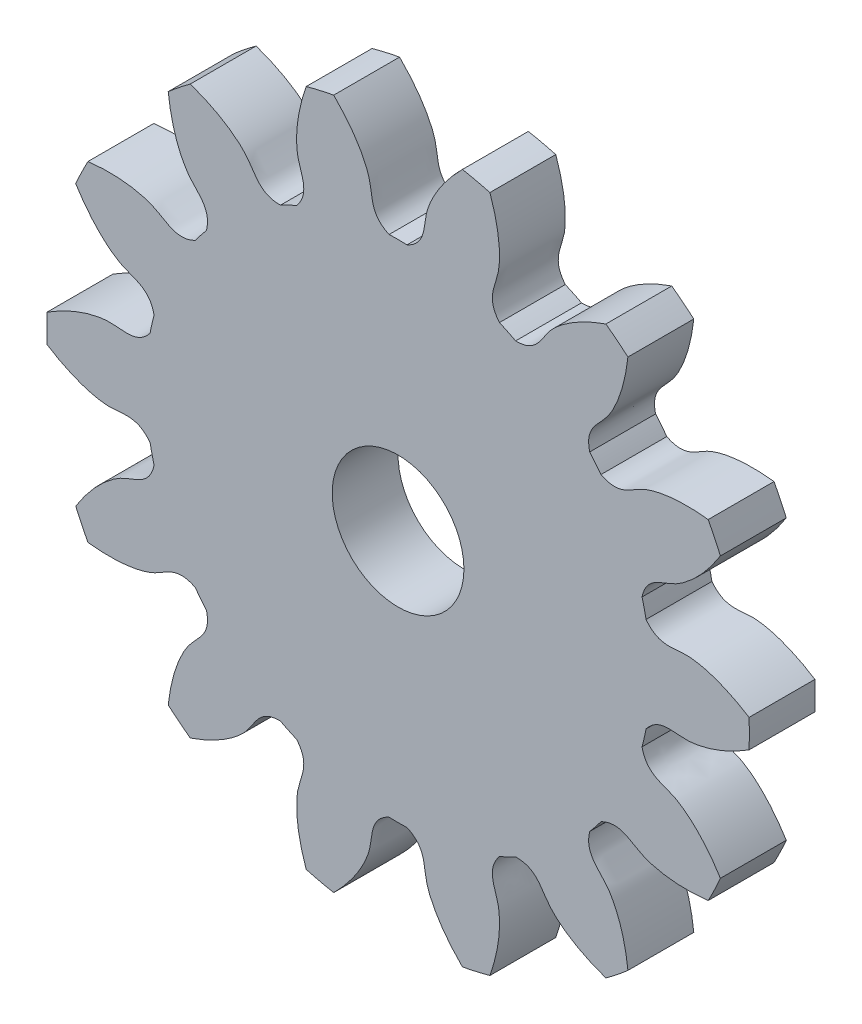
SolidWorks part; units mm, degrees
material "Thornel Mat VMA"
ref_plane "前视基准面" through (0, 0, 0) normal (0, 0, 1) x (1, 0, 0)
ref_plane "上视基准面" through (0, 0, 0) normal (0, 1, 0) x (1, 0, 0)
ref_plane "右视基准面" through (0, 0, 0) normal (1, 0, 0) x (0, 0, -1)
sketch "草图1" plane through (0, 0, 0) normal (0, 0, 1) x (1, 0, 0)
  circle A0 centre (0, 0) radius 16
extrude "凸台-拉伸1" add sketch "草图1" along normal mid plane 3
ref_axis "基准轴1" through (0, 0, -0.15) along (0, 0, 1)
sketch "草图2" plane through (0, 0, 0) normal (0, 0, 1) x (1, 0, 0)
  line L0 (0, 0) -> (0, 16) construction
  circle A0 centre (0, 0) radius 16 construction
  arc A1 (0.4086, 11.4927) -> (-0.4086, 11.4927) centre (0, 0) ccw
  arc A2 (6.4478, 18.0544) -> (-6.4478, 18.0544) centre (0, 0) ccw
  spline S0 degree 3 poles (0.4086, 11.4927) (1.2933, 11.896) (1.1435, 12.6342) (1.3273, 13.3028) (1.3415, 13.3508) (1.3583, 13.4034) (1.3778, 13.4607) (1.4002, 13.5225) (1.4258, 13.5888) (1.4546, 13.6595) (1.487, 13.7344) (1.523, 13.8134) (1.5629, 13.8964) (1.6068, 13.9833) (1.6549, 14.0739) (1.7073, 14.1682) (1.7643, 14.2659) (1.826, 14.367) (1.8925, 14.4713) (1.964, 14.5786) (2.0406, 14.6888) (2.1225, 14.8016) (2.2098, 14.917) (2.3027, 15.0348) (2.4012, 15.1548) (2.5056, 15.2767) (2.6158, 15.4005) (2.7321, 15.5259) (2.8546, 15.6528) (2.9832, 15.7809) (3.1182, 15.91) (3.2597, 16.04) (3.4076, 16.1705) (3.5622, 16.3016) (3.7234, 16.4328) (3.8914, 16.564) (4.0661, 16.6949) (4.2478, 16.8255) (4.4363, 16.9553) (4.6318, 17.0843) (4.8342, 17.2121) (5.0437, 17.3386) (5.2603, 17.4635) (5.4839, 17.5865) (5.7145, 17.7076) (6.0347, 17.8675) (6.2807, 17.9812) (6.4478, 18.0544) knots 0 0 0 0 0.215624 0.220482 0.225911 0.231912 0.238484 0.245628 0.253343 0.26163 0.270488 0.279917 0.289919 0.300491 0.311635 0.323351 0.335638 0.348497 0.361927 0.375928 0.390502 0.405646 0.421362 0.43765 0.454509 0.471939 0.489942 0.508515 0.52766 0.547377 0.567665 0.588524 0.609955 0.631958 0.654532 0.677677 0.701394 0.725683 0.750543 0.775974 0.801977 0.828552 0.855698 0.883415 0.911704 0.940565 1 1 1 1
  spline S1 degree 3 poles (-0.4086, 11.4927) (-1.2933, 11.896) (-1.1435, 12.6342) (-1.3273, 13.3028) (-1.3415, 13.3508) (-1.3583, 13.4034) (-1.3778, 13.4607) (-1.4002, 13.5225) (-1.4258, 13.5888) (-1.4546, 13.6595) (-1.487, 13.7344) (-1.523, 13.8134) (-1.5629, 13.8964) (-1.6068, 13.9833) (-1.6549, 14.0739) (-1.7073, 14.1682) (-1.7643, 14.2659) (-1.826, 14.367) (-1.8925, 14.4713) (-1.964, 14.5786) (-2.0406, 14.6888) (-2.1225, 14.8016) (-2.2098, 14.917) (-2.3027, 15.0348) (-2.4012, 15.1548) (-2.5056, 15.2767) (-2.6158, 15.4005) (-2.7321, 15.5259) (-2.8546, 15.6528) (-2.9832, 15.7809) (-3.1182, 15.91) (-3.2597, 16.04) (-3.4076, 16.1705) (-3.5622, 16.3016) (-3.7234, 16.4328) (-3.8914, 16.564) (-4.0661, 16.6949) (-4.2478, 16.8255) (-4.4363, 16.9553) (-4.6318, 17.0843) (-4.8342, 17.2121) (-5.0437, 17.3386) (-5.2603, 17.4635) (-5.4839, 17.5865) (-5.7145, 17.7076) (-6.0347, 17.8675) (-6.2807, 17.9812) (-6.4478, 18.0544) knots 0 0 0 0 0.215624 0.220482 0.225911 0.231912 0.238484 0.245628 0.253343 0.26163 0.270488 0.279917 0.289919 0.300491 0.311635 0.323351 0.335638 0.348497 0.361927 0.375928 0.390502 0.405646 0.421362 0.43765 0.454509 0.471939 0.489942 0.508515 0.52766 0.547377 0.567665 0.588524 0.609955 0.631958 0.654532 0.677677 0.701394 0.725683 0.750543 0.775974 0.801977 0.828552 0.855698 0.883415 0.911704 0.940565 1 1 1 1
extrude "切除-拉伸1" cut sketch "草图2" along normal through all both and the other way through all
pattern_circular "阵列(圆周)1" count 14 every 25.714 about axis through (0, 0, -0.15) along (0, 0, 1) of "切除-拉伸1"
sketch "草图3" plane through (0, 0, 0) normal (0, 0, 1) x (1, 0, 0)
  circle A0 centre (0, 0) radius 14 construction
  dimension "Dn" = 28
sketch "草图4" plane through (0, 0, 1.5) normal (0, 0, 1) x (1, 0, 0)
  circle A0 centre (0, 0) radius 3
  dimension "D1" = 6
extrude "切除-拉伸2" cut sketch "草图4" against normal mid plane 10
